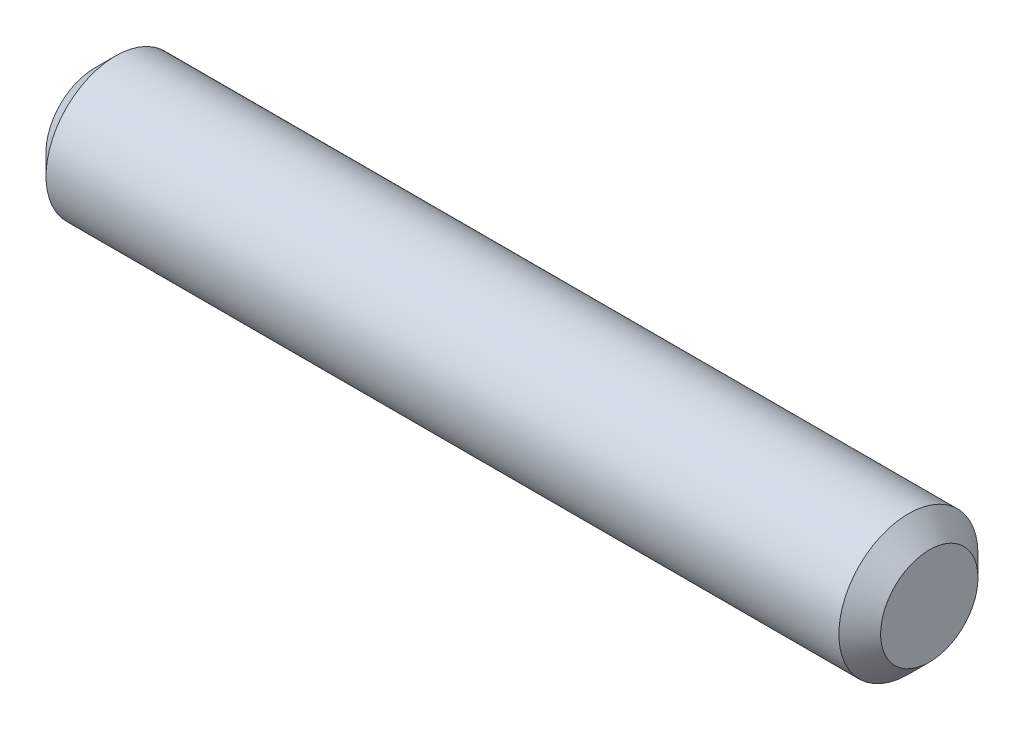
SolidWorks part; units mm, degrees
material "Plain Carbon Steel"
ref_plane "Front Plane" through (0, 0, 0) normal (0, 0, 1) x (1, 0, 0)
ref_plane "Top Plane" through (0, 0, 0) normal (0, 1, 0) x (1, 0, 0)
ref_plane "Right Plane" through (0, 0, 0) normal (1, 0, 0) x (0, 0, -1)
sketch "Sketch1" plane through (0, 0, 0) normal (0, 0, 1) x (1, 0, 0)
  line L0 (-19.05, 0) -> (19.05, 0) construction
  line L1 (19.05, 3.175) -> (19.05, -3.175) construction
  line L2 (-19.05, 3.175) -> (-19.05, -3.175) construction
  line L3 (19.05, 3.175) -> (-63.5, 3.175) construction
  point P6 (14.605, -3.175)
  point P9 (-6.35, 0)
  point P10 (6.35, 0)
  point P11 (19.05, 0)
  point P12 (-19.05, 0)
  dimension "D1" = 4.445
  dimension "D2" = 12.7
  dimension "D3" = 12.7
  dimension "D4" = 25.4
  dimension "D5" = 25.4
sketch "Sketch2" plane through (0, 0, 0) normal (1, 0, 0) x (0, 0, -1)
  circle A0 centre (0, 0) radius 3.175
extrude "Boss-Extrude1" add sketch "Sketch2" against normal up to vertex (19.05 mm away) and the other way up to vertex (19.05 mm away) up to point (-19.05, 0, 0) other way up to point (19.05, 0, 0)
chamfer "Chamfer1" distance 0.9525 angle 45 2 edges at (-19.05, 0, -3.175) (19.05, 0, -3.175)
sketch "Drawing1" plane through (0, 0, 0) normal (1, 0, 0) x (0, 0, -1)
  circle A0 centre (0, 0) radius 3.175
sketch "Sketch3" [suppressed] plane through (152.4, 0, 0) normal (1, 0, 0) x (0, 0, -1)
  circle A1 centre (0, 0) radius 3.175
  circle A2 centre (0, 0) radius 3.175
  dimension "D1" = 0
curve "Helix/Spiral1" [suppressed] pitch 1.27 height 83.82 turns 66 parameters "Pitch"=1.27
sketch "Sketch4" [suppressed] plane through (0, 0, 0) normal (0, 0, 1) x (1, 0, 0)
  line L0 (152.9556, 2.3501) -> (152.9556, 3.175) construction
  line L1 (152.6381, 2.7626) -> (153.2731, 2.7626) construction
  line L2 (151.9237, 3.9999) -> (152.8763, 2.3501)
  line L3 (153.9875, 3.9999) -> (153.035, 2.3501)
  line L4 (151.9237, 3.9999) -> (153.9875, 3.9999)
  line L5 (152.8763, 2.3501) -> (153.035, 2.3501) construction
  line L7 (152.8763, 2.3501) -> (152.4, 3.175) construction
  line L8 (152.8763, 2.3501) -> (153.035, 2.3501)
  line L9 (152.4, 3.175) -> (153.5113, 3.175) construction
  line L10 (153.5113, 3.175) -> (153.035, 2.3501) construction
  point P9 (152.4, 3.175)
  point P11 (153.5113, 3.175)
  dimension "D2" = 0.1588
  dimension "D1" = 0.635
  dimension "D3" = 60
sweep "Cut-Sweep3" [suppressed] cut profiles "Sketch4" path "Helix/Spiral1"
pattern_linear "LPattern1" [suppressed] count 1 spacing 81.28 along (-1, 0, 0) of bodies 102
ref_plane "Plane1" [suppressed] through (-114.3, 0, 0) normal (1, 0, 0) x (0, 0, -1)
ref_plane "Plane2" [suppressed] through (114.3, 0, 0) normal (1, 0, 0) x (0, 0, -1)
split "Split1" [suppressed] bodies to split 103
equation "\"D3@Helix/Spiral1\"=\"Pitch@Helix/Spiral1\"+\"Segment Length@Sketch1\""
equation "\"D1@Chamfer1\" = \"Pitch@Helix/Spiral1\"*.75"
equation "\"D2@Sketch4\"=\"Pitch@Helix/Spiral1\"*.125"
equation "\"D1@Sketch1\" = \"Pitch@Helix/Spiral1\"*3.50"
equation "\"Segment Length@Sketch1\" = \"Pitch@Helix/Spiral1\"*65"
equation "\"D1@LPattern1\"=(\"Length@Sketch1\"/(\"Segment Length@Sketch1\"-\"Pitch@Helix/Spiral1\"))+1"
equation "\"D3@LPattern1\"=\"Segment Length@Sketch1\"-\"Pitch@Helix/Spiral1\""
equation "\"D2@Sketch1\"=\"Thread Diameter@Sketch1\"*2"
equation "\"D3@Sketch1\"=\"Thread Diameter@Sketch1\"*2"
equation "\"D1@Sketch4\"=\"Pitch@Helix/Spiral1\"*.5"
